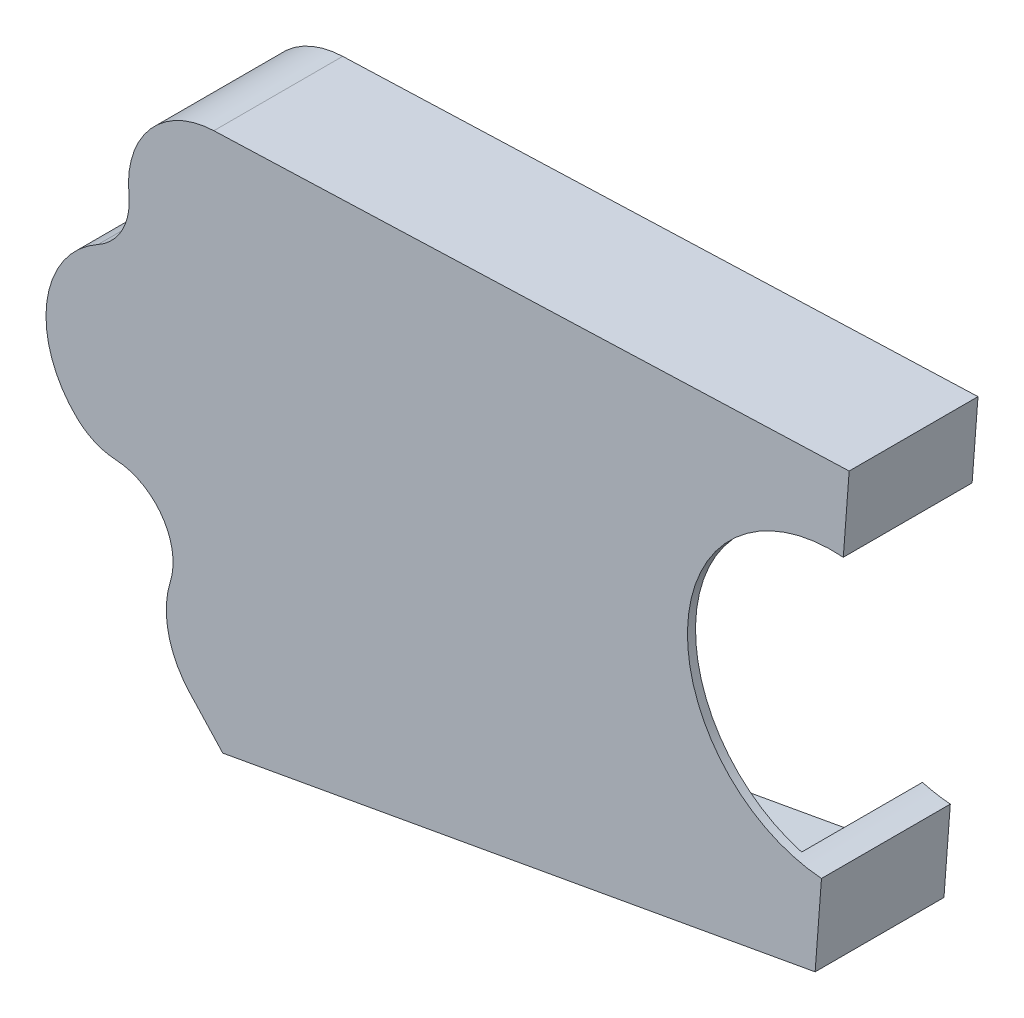
SolidWorks part; units mm, degrees
ref_plane "Front Plane" through (0, 0, 0) normal (0, 0, 1) x (1, 0, 0)
ref_plane "Top Plane" through (0, 0, 0) normal (0, 1, 0) x (1, 0, 0)
ref_plane "Right Plane" through (0, 0, 0) normal (1, 0, 0) x (0, 0, -1)
sketch "Sketch1" plane through (0, 0, 0) normal (0, 0, 1) x (1, 0, 0)
  line L8 (-119.5948, -74.4106) -> (-92.5405, -103.7404)
  line L9 (-119.5948, -74.4106) -> (-92.5405, -103.7404)
  line L10 (-71.3446, -104.5958) -> (-37.2211, -73.1197)
  line L11 (-71.3446, -104.5958) -> (-37.2211, -73.1197)
  line L16 (-27.1401, -68.1042) -> (68.9251, -50.7959)
  line L17 (-111.4072, -83.2869) -> (68.9251, -50.7959)
  line L18 (56.0883, 55.6165) -> (-113.6124, 49.4857)
  line L19 (56.0883, 55.6165) -> (-113.6124, 49.4857)
  line L20 (-114.4495, -69.6645) -> (-87.3952, -98.9943)
  line L21 (-114.4495, -69.6645) -> (-87.3952, -98.9943)
  line L22 (-76.0907, -99.4505) -> (-41.9673, -67.9744)
  line L23 (-76.0907, -99.4505) -> (-41.9673, -67.9744)
  line L28 (-28.3813, -61.2151) -> (67.6838, -43.9068)
  line L29 (-108.8671, -75.7165) -> (67.6838, -43.9068)
  line L30 (56.341, 48.621) -> (-113.3597, 42.4902)
  line L31 (56.341, 48.621) -> (-113.3597, 42.4902)
  line L32 (44.1846, 55.1864) -> (35.7309, -56.7765)
  line L33 (-27.1401, -68.1042) -> (68.9251, -50.7959) construction
  line L34 (-113.6124, 49.4857) -> (56.0883, 55.6165) construction
  line L35 (-111.6252, 43.3) -> (42.409, 31.6699) construction
  line L36 (36.6151, 47.9084) -> (29.1586, -50.848)
  arc A22 (-124.4228, -52.9336) -> (-137.9704, -33.4802) centre (-138.7403, -48.4604) ccw
  arc A23 (-124.4228, -52.9336) -> (-137.9704, -33.4802) centre (-138.7403, -48.4604) ccw
  arc A24 (-124.4228, -52.9336) -> (-119.5948, -74.4106) centre (-103.4238, -59.4942) ccw
  arc A25 (-124.4228, -52.9336) -> (-119.5948, -74.4106) centre (-103.4238, -59.4942) ccw
  arc A26 (-92.5405, -103.7404) -> (-71.3446, -104.5958) centre (-81.5148, -93.5701) ccw
  arc A27 (-92.5405, -103.7404) -> (-71.3446, -104.5958) centre (-81.5148, -93.5701) ccw
  arc A28 (-27.1401, -68.1042) -> (-37.2211, -73.1197) centre (-23.5699, -87.9191) ccw
  arc A29 (-27.1401, -68.1042) -> (-37.2211, -73.1197) centre (-23.5699, -87.9191) ccw
  arc A30 (68.9251, -50.7959) -> (91, -33.5) centre (63.6055, -21.2712) ccw
  arc A31 (68.9251, -50.7959) -> (91, -33.5) centre (63.6055, -21.2712) ccw
  arc A32 (91, -33.5) -> (80.2612, 44.7896) centre (22.6589, -2.9929) ccw
  arc A44 (91, -33.5) -> (80.2612, 44.7896) centre (22.6589, -2.9929) ccw
  arc A45 (80.2612, 44.7896) -> (56.0883, 55.6165) centre (57.1714, 25.636) ccw
  arc A46 (80.2612, 44.7896) -> (56.0883, 55.6165) centre (57.1714, 25.636) ccw
  arc A47 (-113.6124, 49.4857) -> (-134.7058, 25.2795) centre (-112.8181, 27.5) ccw
  arc A48 (-113.6124, 49.4857) -> (-134.7058, 25.2795) centre (-112.8181, 27.5) ccw
  arc A49 (-142.3827, 10.6321) -> (-134.7058, 25.2795) centre (-149.6292, 23.7656) ccw
  arc A50 (-142.3827, 10.6321) -> (-134.7058, 25.2795) centre (-149.6292, 23.7656) ccw
  arc A51 (-142.3827, 10.6321) -> (-147.5429, -29.3643) centre (-130.3054, -11.2571) ccw
  arc A52 (-142.3827, 10.6321) -> (-147.5429, -29.3643) centre (-130.3054, -11.2571) ccw
  arc A53 (-147.5429, -29.3643) -> (-137.9704, -33.4802) centre (-137.2004, -18.5) ccw
  arc A54 (-147.5429, -29.3643) -> (-137.9704, -33.4802) centre (-137.2004, -18.5) ccw
  arc A55 (-117.7413, -55.0211) -> (-137.611, -26.4895) centre (-138.7403, -48.4604) ccw
  arc A56 (-117.7413, -55.0211) -> (-137.611, -26.4895) centre (-138.7403, -48.4604) ccw
  arc A57 (-117.7413, -55.0211) -> (-114.4495, -69.6645) centre (-103.4238, -59.4942) ccw
  arc A58 (-117.7413, -55.0211) -> (-114.4495, -69.6645) centre (-103.4238, -59.4942) ccw
  arc A59 (-87.3952, -98.9943) -> (-76.0907, -99.4505) centre (-81.5148, -93.5701) ccw
  arc A60 (-87.3952, -98.9943) -> (-76.0907, -99.4505) centre (-81.5148, -93.5701) ccw
  arc A61 (-28.3813, -61.2151) -> (-41.9673, -67.9744) centre (-23.5699, -87.9191) ccw
  arc A62 (-28.3813, -61.2151) -> (-41.9673, -67.9744) centre (-23.5699, -87.9191) ccw
  arc A63 (67.6838, -43.9068) -> (84.608, -30.6466) centre (63.6055, -21.2712) ccw
  arc A73 (67.6838, -43.9068) -> (84.608, -30.6466) centre (63.6055, -21.2712) ccw
  arc A74 (84.608, -30.6466) -> (74.8736, 40.3204) centre (22.6589, -2.9929) ccw
  arc A75 (84.608, -30.6466) -> (74.8736, 40.3204) centre (22.6589, -2.9929) ccw
  arc A76 (74.8736, 40.3204) -> (56.341, 48.621) centre (57.1714, 25.636) ccw
  arc A77 (74.8736, 40.3204) -> (56.341, 48.621) centre (57.1714, 25.636) ccw
  arc A78 (-113.3597, 42.4902) -> (-127.7415, 25.986) centre (-112.8181, 27.5) ccw
  arc A79 (-113.3597, 42.4902) -> (-127.7415, 25.986) centre (-112.8181, 27.5) ccw
  arc A80 (-139.0011, 4.5031) -> (-127.7415, 25.986) centre (-149.6292, 23.7656) ccw
  arc A81 (-139.0011, 4.5031) -> (-127.7415, 25.986) centre (-149.6292, 23.7656) ccw
  arc A82 (-139.0011, 4.5031) -> (-142.7164, -24.2943) centre (-130.3054, -11.2571) ccw
  arc A83 (-139.0011, 4.5031) -> (-142.7164, -24.2943) centre (-130.3054, -11.2571) ccw
  arc A84 (-142.7164, -24.2943) -> (-137.611, -26.4895) centre (-137.2004, -18.5) ccw
  arc A85 (-142.7164, -24.2943) -> (-137.611, -26.4895) centre (-137.2004, -18.5) ccw
  circle A86 centre (40.0178, 0) radius 36
  arc A87 (5.9892, -8.1888) -> (30.6476, -33.7224) centre (40.0178, 0) ccw construction
  dimension "D4" = 1
  dimension "D3" = 7
  dimension "D1" = 0
  dimension "D2" = 7
extrude "Boss-Extrude1" add sketch "Sketch1" along normal blind 30 contours A52 A54 A23 A25 L9 A27 L11 A29 L17 A31 A44 A46 L19 A48 A50 A85 A83 A81 A79 L31 A77 A75 A73 L29 A62 L23 A60 L21 A58 A56 | A62 L29 L21 L17 L23 | L29 A62 L23 L17 L32 | A86 L36 L29 L32 | A86 L32 L31 L36 region at (-122.5189, -63.7868, 0) region at (-72.9993, -72.6407, 0) region at (-2.1687, -60.1476, 0) region at (33.1772, -42.8072, 0) region at (39.6825, 41.9847, 0)
sketch "Sketch3" plane through (0, 0, 30) normal (0, 0, 1) x (1, 0, 0)
  line L0 (-65.2656, 44.2277) -> (121.4688, -34.2162)
  line L1 (-113.3597, 42.4902) -> (36.6151, 47.9084) construction
  line L2 (29.1586, -50.848) -> (-108.8671, -75.7165) construction
  point P6 (-50.3651, 44.766)
  dimension "D1" = 33
sketch "Sketch4" plane through (0, 0, 30) normal (0, 0, 1) x (1, 0, 0)
  line L21 (-113.3597, 42.4902) -> (36.6151, 47.9084)
  line L22 (36.6151, 47.9084) -> (35.6963, 35.7397)
  line L23 (42.7282, 35.8978) -> (44.1846, 55.1864)
  line L24 (44.1846, 55.1864) -> (-113.6124, 49.4857)
  line L25 (-119.5948, -74.4106) -> (-111.4072, -83.2869)
  line L26 (-111.4072, -83.2869) -> (35.7309, -56.7765)
  line L27 (35.7309, -56.7765) -> (37.3074, -35.8978)
  line L28 (30.379, -34.6856) -> (29.1586, -50.848)
  line L29 (29.1586, -50.848) -> (-108.8671, -75.7165)
  line L30 (-108.8671, -75.7165) -> (-114.4495, -69.6645)
  line L31 (-113.3597, 42.4902) -> (36.6151, 47.9084)
  line L32 (36.6151, 47.9084) -> (35.6963, 35.7397)
  line L33 (42.7282, 35.8978) -> (44.1846, 55.1864)
  line L34 (44.1846, 55.1864) -> (-113.6124, 49.4857)
  line L35 (-119.5948, -74.4106) -> (-111.4072, -83.2869)
  line L36 (-111.4072, -83.2869) -> (35.7309, -56.7765)
  line L37 (35.7309, -56.7765) -> (37.3074, -35.8978)
  line L38 (30.379, -34.6856) -> (29.1586, -50.848)
  line L39 (29.1586, -50.848) -> (-108.8671, -75.7165)
  line L40 (-108.8671, -75.7165) -> (-114.4495, -69.6645)
  circle A14 centre (40.0178, 0) radius 36
  arc A28 (-142.7164, -24.2943) -> (-137.611, -26.4895) centre (-137.2004, -18.5) ccw
  arc A29 (-139.0011, 4.5031) -> (-142.7164, -24.2943) centre (-130.3054, -11.2571) ccw
  arc A30 (-139.0011, 4.5031) -> (-127.7415, 25.986) centre (-149.6292, 23.7656) ccw
  arc A31 (-113.3597, 42.4902) -> (-127.7415, 25.986) centre (-112.8181, 27.5) ccw
  arc A32 (42.7282, 35.8978) -> (35.6963, 35.7397) centre (40.0178, 0) ccw
  arc A33 (-113.6124, 49.4857) -> (-134.7058, 25.2795) centre (-112.8181, 27.5) ccw
  arc A34 (-142.3827, 10.6321) -> (-134.7058, 25.2795) centre (-149.6292, 23.7656) ccw
  arc A35 (-142.3827, 10.6321) -> (-147.5429, -29.3643) centre (-130.3054, -11.2571) ccw
  arc A36 (-147.5429, -29.3643) -> (-137.9704, -33.4802) centre (-137.2004, -18.5) ccw
  arc A37 (-124.4228, -52.9336) -> (-137.9704, -33.4802) centre (-138.7403, -48.4604) ccw
  arc A38 (-124.4228, -52.9336) -> (-119.5948, -74.4106) centre (-103.4238, -59.4942) ccw
  arc A39 (30.379, -34.6856) -> (37.3074, -35.8978) centre (40.0178, 0) ccw
  arc A40 (-117.7413, -55.0211) -> (-114.4495, -69.6645) centre (-103.4238, -59.4942) ccw
  arc A41 (-117.7413, -55.0211) -> (-137.611, -26.4895) centre (-138.7403, -48.4604) ccw
  arc A42 (-142.7164, -24.2943) -> (-137.611, -26.4895) centre (-137.2004, -18.5) ccw
  arc A43 (-139.0011, 4.5031) -> (-142.7164, -24.2943) centre (-130.3054, -11.2571) ccw
  arc A44 (-139.0011, 4.5031) -> (-127.7415, 25.986) centre (-149.6292, 23.7656) ccw
  arc A45 (-113.3597, 42.4902) -> (-127.7415, 25.986) centre (-112.8181, 27.5) ccw
  arc A46 (42.7282, 35.8978) -> (35.6963, 35.7397) centre (40.0178, 0) ccw
  arc A47 (-113.6124, 49.4857) -> (-134.7058, 25.2795) centre (-112.8181, 27.5) ccw
  arc A48 (-142.3827, 10.6321) -> (-134.7058, 25.2795) centre (-149.6292, 23.7656) ccw
  arc A49 (-142.3827, 10.6321) -> (-147.5429, -29.3643) centre (-130.3054, -11.2571) ccw
  arc A50 (-147.5429, -29.3643) -> (-137.9704, -33.4802) centre (-137.2004, -18.5) ccw
  arc A51 (-124.4228, -52.9336) -> (-137.9704, -33.4802) centre (-138.7403, -48.4604) ccw
  arc A52 (-124.4228, -52.9336) -> (-119.5948, -74.4106) centre (-103.4238, -59.4942) ccw
  arc A53 (30.379, -34.6856) -> (37.3074, -35.8978) centre (40.0178, 0) ccw
  arc A54 (-117.7413, -55.0211) -> (-114.4495, -69.6645) centre (-103.4238, -59.4942) ccw
  arc A55 (-117.7413, -55.0211) -> (-137.611, -26.4895) centre (-138.7403, -48.4604) ccw
  arc M25 (-137.611, -26.4895) -> (-142.7164, -24.2943) centre (-137.2004, -18.5) cw
  arc M26 (-142.7164, -24.2943) -> (-139.0011, 4.5031) centre (-130.3054, -11.2571) cw
  arc M27 (-139.0011, 4.5031) -> (-127.7415, 25.986) centre (-149.6292, 23.7656) ccw
  arc M28 (-127.7415, 25.986) -> (-113.3597, 42.4902) centre (-112.8181, 27.5) cw
  line M29 (-113.3597, 42.4902) -> (36.6151, 47.9084)
  line M30 (36.6151, 47.9084) -> (35.6963, 35.7397)
  arc M31 (35.6963, 35.7397) -> (42.7282, 35.8978) centre (40.0178, 0) cw
  line M32 (42.7282, 35.8978) -> (44.1846, 55.1864)
  line M33 (44.1846, 55.1864) -> (-113.6124, 49.4857)
  arc M34 (-113.6124, 49.4857) -> (-134.7058, 25.2795) centre (-112.8181, 27.5) ccw
  arc M35 (-134.7058, 25.2795) -> (-142.3827, 10.6321) centre (-149.6292, 23.7656) cw
  arc M36 (-142.3827, 10.6321) -> (-147.5429, -29.3643) centre (-130.3054, -11.2571) ccw
  arc M37 (-147.5429, -29.3643) -> (-137.9704, -33.4802) centre (-137.2004, -18.5) ccw
  arc M38 (-137.9704, -33.4802) -> (-124.4228, -52.9336) centre (-138.7403, -48.4604) cw
  arc M39 (-124.4228, -52.9336) -> (-119.5948, -74.4106) centre (-103.4238, -59.4942) ccw
  line M40 (-119.5948, -74.4106) -> (-111.4072, -83.2869)
  line M41 (-111.4072, -83.2869) -> (35.7309, -56.7765)
  line M42 (35.7309, -56.7765) -> (37.3074, -35.8978)
  arc M43 (37.3074, -35.8978) -> (30.379, -34.6856) centre (40.0178, 0) cw
  line M44 (30.379, -34.6856) -> (29.1586, -50.848)
  line M45 (29.1586, -50.848) -> (-108.8671, -75.7165)
  line M46 (-108.8671, -75.7165) -> (-114.4495, -69.6645)
  arc M47 (-114.4495, -69.6645) -> (-117.7413, -55.0211) centre (-103.4238, -59.4942) cw
  arc M48 (-117.7413, -55.0211) -> (-137.611, -26.4895) centre (-138.7403, -48.4604) ccw
  dimension "D1" = 0
extrude "Boss-Extrude2" add sketch "Sketch4" along normal blind 2 contours A14 M30 M29 M28 M27 M26 M25 M48 M47 M46 M45 M44 | M48 M25 M26 M27 M28 M29 M30 M31 M32 M33 M34 M35 M36 M37 M38 M39 M40 M41 M42 M43 M44 M45 M46 M47 region at (-125.9577, 38.9499, 30) region at (-57.9317, -9.5661, 30)
